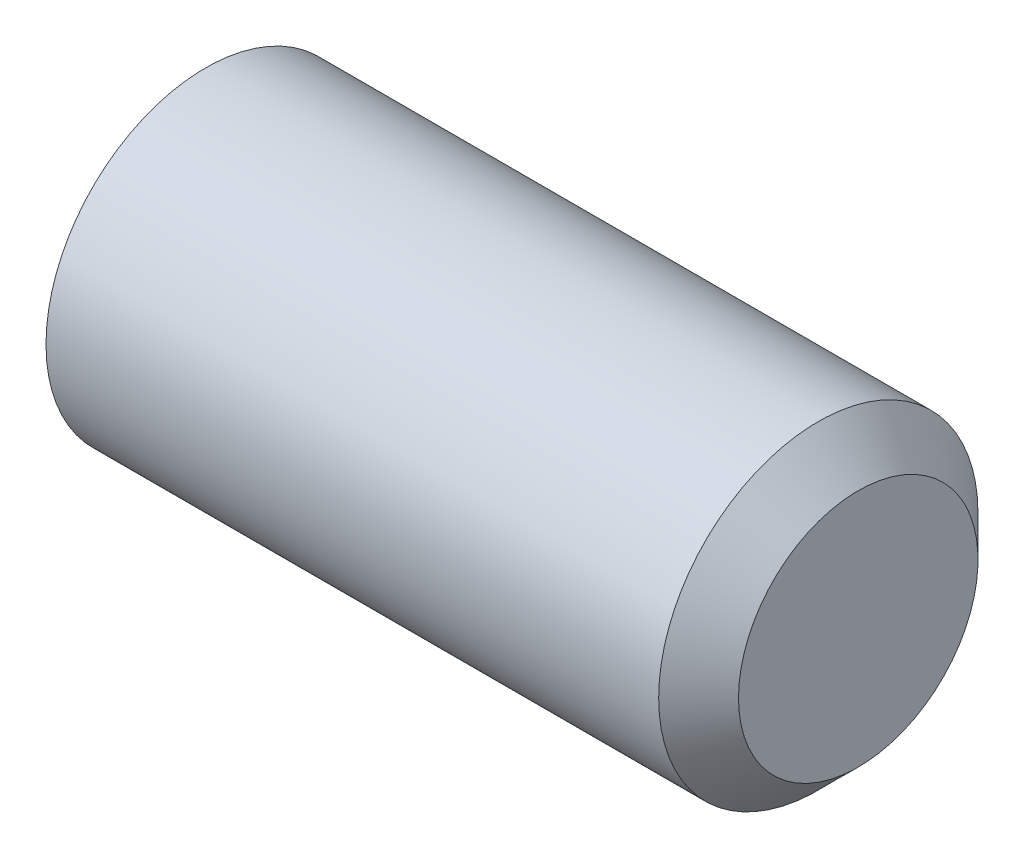
SolidWorks part; units mm, degrees
revolve "BaseBody" add sketch "BodySke" angle 360 about L5 other way angle 60
sketch "BodySke" plane through (0, 0, 0) normal (0, 0, 1) x (1, 0, 0)
  line L0 (0, 0) -> (0, 10.352)
  line L1 (0, 10.352) -> (0.9515, 12)
  line L2 (0.9515, 12) -> (47, 12)
  line L3 (47, 12) -> (50, 9)
  line L4 (50, 0) -> (0, 0)
  line L5 (-12.7, 0) -> (88.9, 0) construction
  line L6 (50, 9) -> (50, 0)
  line L7 (50, 9) -> (50, 18.525) construction
  line L8 (0, -10.352) -> (0.9515, -12) construction
  line L9 (3, 15.875) -> (3, -3.175) construction
  line L10 (47, -12) -> (50, -9) construction
  dimension "Length" = 50
  dimension "Diameter" = 24
cosmetic thread "ThreadCosmetic" [suppressed] parameters "Thread_minor"=20.704
ref_plane "Plane1" through (0, 0, 0) normal (0, 0, 1) x (1, 0, 0)
ref_plane "Plane2" through (0, 0, 0) normal (0, 1, 0) x (1, 0, 0)
ref_plane "Plane3" through (0, 0, 0) normal (1, 0, 0) x (0, 0, -1)
sketch "Sketch2" plane through (0, 0, 0) normal (-1, 0, 0) x (0, 0, 1)
  line L0 (3.4641, 6) -> (-3.4641, 6)
  line L1 (-3.4641, 6) -> (-6.9282, 0)
  line L2 (3.4641, 6) -> (6.9282, 0)
  line L3 (3.4641, -6) -> (6.9282, 0)
  line L4 (3.4641, -6) -> (-3.4641, -6)
  line L5 (-3.4641, -6) -> (-6.9282, 0)
  dimension "D2" = 6
  dimension "D3" = 6
extrude "Hex" cut sketch "Sketch2" against normal blind 15
sketch "ThdSchSke" plane through (0, 0, 0) normal (0, 0, 1) x (1, 0, 0)
  line L0 (0.9515, -10.352) -> (-0.2025, -12)
  line L1 (0.9515, -10.352) -> (2.1054, -12)
  line L2 (2.1054, -12) -> (2.1054, -15)
  line L3 (-3.175, 0) -> (5.1513, 0) construction
  line L5 (2.1054, -15) -> (-0.2025, -15)
  line L6 (-0.2025, -15) -> (-0.2025, -12)
  line L8 (0.9515, 12) -> (0.9515, -12) construction
  dimension "Thread_minor" = 20.704
  dimension "Diameter" = 24
revolve "ThreadSchematic" [suppressed] cut sketch "ThdSchSke" angle 360 about L3
pattern_linear "ThdSchPat" [suppressed]
equation "\"D2@Sketch2\" = \"Hex_size@Sketch2\" / 2"
equation "\"D3@Sketch2\" = \"Hex_size@Sketch2\" / 2"
equation "\"Thread_minor@ThreadCosmetic\" = \"Minor_dia@BodySke\""
equation "\"Thread_minor@ThdSchSke\" = \"Thread_minor@ThreadCosmetic\""
equation "\"Diameter@ThdSchSke\" = \"Diameter@BodySke\""
equation "\"Overcut@ThdSchSke\" = \"Diameter@BodySke\" * 1.25"
equation "\"Num_threads@ThdSchPat\" = int( (\"Length@BodySke\" - ( ( ( \"Diameter@BodySke\" - \"Minor_dia@BodySke\" ) * 0.5 ) / tan( \"Drive_ch_ang@BodySke\" * 0.017453292 ) ) - ( ( ( \"Diameter@BodySke\" - \"Cup_dia@BodySke\" ) * 0.5 ) * tan( \"Cup_nose_ang@BodySke\" * 0.017453292 ) ) ) / \"Advance@BodySke\" + 0.999 )  + 1"
equation "\"Advance@ThdSchPat\" = (\"Length@BodySke\" - ( ( ( \"Diameter@BodySke\" - \"Minor_dia@BodySke\" ) * 0.5 ) / tan( \"Drive_ch_ang@BodySke\" * 0.017453292 ) ) - ( ( ( \"Diameter@BodySke\" - \"Cup_dia@BodySke\" ) * 0.5 ) * tan( \"Cup_nose_ang@BodySke\" * 0.017453292 ) ) ) /  (\"Num_threads@ThdSchPat\" - 1) 'relax it"
equation "' \"Num_threads@ThdSchPat\" = \"Num_threads@ThdSchPat\" - sgn( \"Num_threads@ThdSchPat\" - 1) '---chamfered tips only---"
